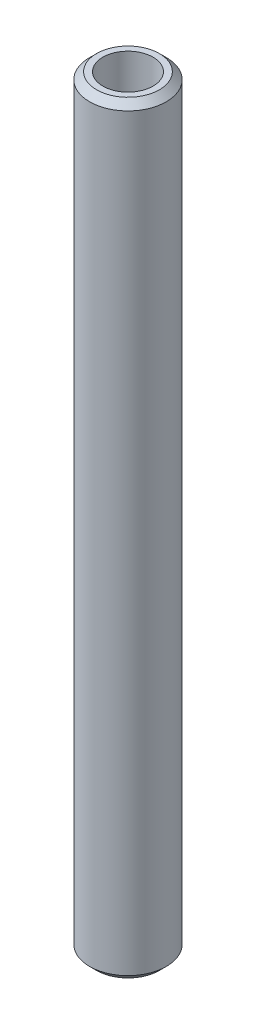
SolidWorks part; units mm, degrees
ref_plane "Front Plane" through (0, 0, 0) normal (0, 0, 1) x (1, 0, 0)
ref_plane "Top Plane" through (0, 0, 0) normal (0, 1, 0) x (1, 0, 0)
ref_plane "Right Plane" through (0, 0, 0) normal (1, 0, 0) x (0, 0, -1)
sketch "Sketch1" plane through (0, 0, 0) normal (0, 1, 0) x (1, 0, 0)
  circle A0 centre (0, 0) radius 10
  dimension "SHAFT_OD" = 20
extrude "Boss-Extrude1" add sketch "Sketch1" along normal blind 198.8924
sketch "Sketch2" plane through (0, 0, 0) normal (0, 1, 0) x (1, 0, 0)
  circle A0 centre (0, 0) radius 6.5496
  dimension "BORE_D" = 13.0992
extrude "Cut-Extrude1" cut sketch "Sketch2" along normal through all
chamfer "Chamfer1" distance 1.8096 angle 45 2 edges at (0, 198.8924, 10) (0, 0, 10)
